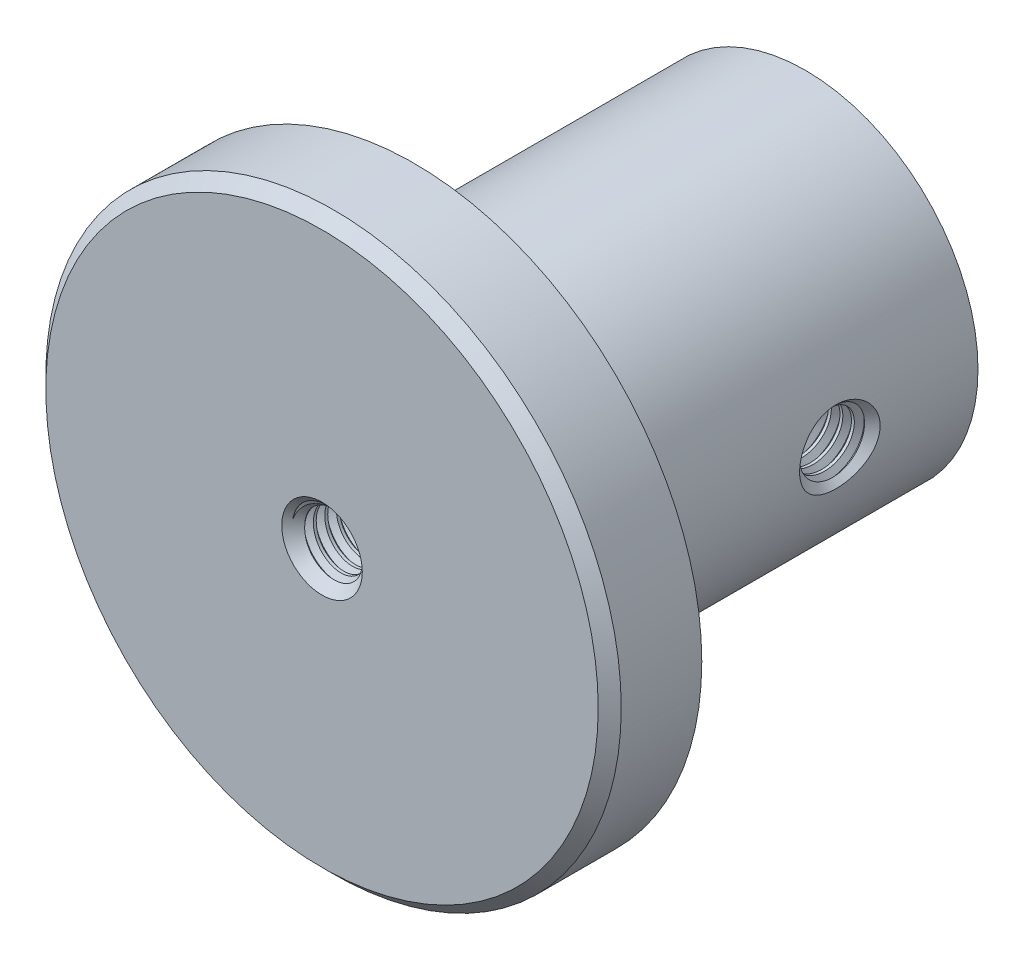
SolidWorks part; units mm, degrees
ref_plane "Front Plane" through (0, 0, 0) normal (0, 0, 1) x (1, 0, 0)
ref_plane "Top Plane" through (0, 0, 0) normal (0, 1, 0) x (1, 0, 0)
ref_plane "Right Plane" through (0, 0, 0) normal (1, 0, 0) x (0, 0, -1)
sketch "Sketch1" plane through (0, 0, 0) normal (0, 0, 1) x (1, 0, 0)
  circle A0 centre (0, 0) radius 12.5
  dimension "D1" = 25
extrude "Boss-Extrude1" add sketch "Sketch1" along normal blind 4
ref_axis "Axis1" through (0, 0, -0.35) along (0, 0, 1)
chamfer "Chamfer1" distance 0.5 angle 45 1 edges at (12.5, 0, 4)
ref_axis "Axis2" through (0, 14.0125, 4) along (0, -1, 0)
sketch "Sketch6" plane through (0, 0, 0) normal (1, 0, 0) x (0, 0, -1)
  line L0 (-4, 14.0125) -> (-4, -13.7625) construction
  line L1 (-4, 8.9) -> (-4, 11.1)
  line L2 (0, 12.5) -> (-3.5, 12.5) construction
  arc A0 (-4, 11.1) -> (-4, 8.9) centre (-4, 10) ccw
  dimension "D1" = 2.2
  dimension "D2" = 2.5
revolve "Cut-Revolve2" [suppressed] cut sketch "Sketch6" angle 360 about L1
pattern_circular "CirPattern1" [suppressed] count 15 over 360 of bodies 112
sketch "Sketch7" plane through (0, 0, 4) normal (0, 0, 1) x (1, 0, 0)
  circle A0 centre (0, 0) radius 1.25
  dimension "D1" = 2.5
extrude "Cut-Extrude1" cut sketch "Sketch7" against normal through all
thread "Thread1" pitch 0.5 method cut profile "Thread Profile1" start angle 0, offset 1, length 0, pitch 0.5, diameter 2.5
ref_plane "Plane1" through (-1.25, 0, 5) normal (0, -1, 0) x (-1, 0, 0)
sketch "Thread Profile1" plane through (-1.25, 0, 5) normal (0, -1, 0) x (-1, 0, 0)
  line L0 (0, 0) -> (0, 0.5) construction
  line L1 (0, 0) -> (0.2706, 0.1562)
  line L2 (0.2706, 0.1562) -> (0.2706, 0.2187)
  line L3 (0.2706, 0.2187) -> (0, 0.375)
  line L4 (0.2706, 0.1875) -> (0, 0.1875) construction
  line L11 (0, 0) -> (0, 0.375)
  point P2 (0, 0)
  dimension "Pitch" = 0.5
  dimension "Profile_Angle" = 60
  dimension "Profile_Land" = 0.0625
  dimension "Profile_Height" = 0.2706
sketch "Sketch10" plane through (0, 0, 4) normal (0, 0, 1) x (1, 0, 0)
  circle A0 centre (0, 0) radius 1.75
  dimension "D1" = 3.5
extrude "Cut-Extrude2" cut sketch "Sketch10" against normal blind 10 draft 45 contours A0
sketch "Sketch11" plane through (0, 0, 0) normal (0, 0, -1) x (-1, 0, 0)
  circle A0 centre (0, 0) radius 7.5
  dimension "D1" = 15
extrude "Boss-Extrude2" add sketch "Sketch11" along normal blind 17 contours A0
sketch "Sketch12" plane through (0, 0, -17) normal (0, 0, -1) x (-1, 0, 0)
  circle A0 centre (0, 0) radius 2.55
  dimension "D1" = 5.1
extrude "Cut-Extrude3" cut sketch "Sketch12" against normal blind 15 contours A0
ref_plane "Plane2" through (7.5, 0, 0) normal (1, 0, 0) x (0, 0, -1)
sketch "Sketch13" plane through (7.5, 0, 0) normal (1, 0, 0) x (0, 0, -1)
  line L0 (17, -7.5) -> (17, 7.5) construction
  circle A0 centre (11, 0) radius 1.25
  dimension "D2" = 2.5
  dimension "D1" = 6
extrude "Cut-Extrude4" cut sketch "Sketch13" against normal up to next contours A0
thread "Thread2" pitch 0.5 method cut profile "Thread Profile2" start angle 0, offset 1, length 8, pitch 0.5, diameter 2.5
ref_plane "Plane3" through (8.5, 0, -9.75) normal (0, -1, 0) x (0, 0, 1)
sketch "Thread Profile2" plane through (8.5, 0, -9.75) normal (0, -1, 0) x (0, 0, 1)
  line L0 (0, 0) -> (0, 0.5) construction
  line L1 (0, 0) -> (0.2706, 0.1562)
  line L2 (0.2706, 0.1562) -> (0.2706, 0.2187)
  line L3 (0.2706, 0.2187) -> (0, 0.375)
  line L4 (0.2706, 0.1875) -> (0, 0.1875) construction
  line L11 (0, 0) -> (0, 0.375)
  point P2 (0, 0)
  dimension "Pitch" = 0.5
  dimension "Profile_Angle" = 60
  dimension "Profile_Land" = 0.0625
  dimension "Profile_Height" = 0.2706
sketch "Sketch16" plane through (7.5, 0, 0) normal (1, 0, 0) x (0, 0, -1)
  circle A0 centre (11, 0) radius 1.75
  dimension "D1" = 3.5
extrude "Cut-Extrude5" cut sketch "Sketch16" against normal blind 15 draft 45
